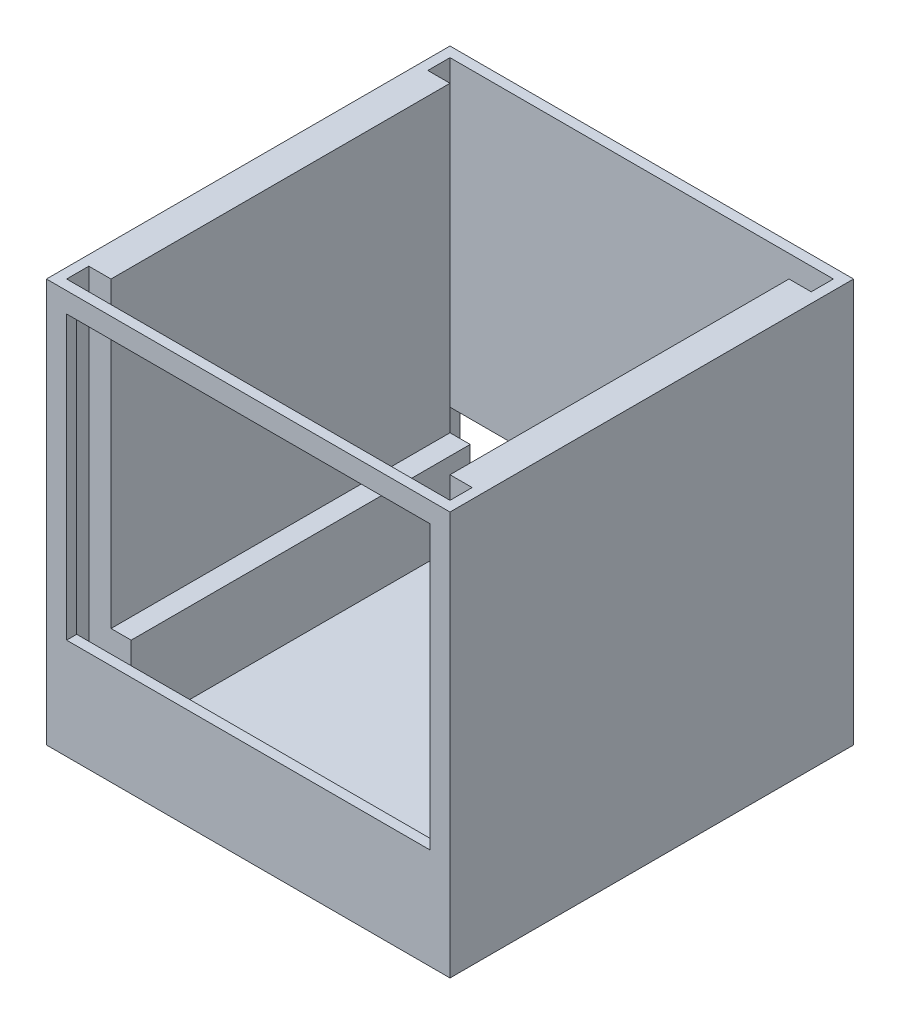
SolidWorks part; units mm, degrees
ref_plane "Front Plane" through (0, 0, 0) normal (0, 0, 1) x (1, 0, 0)
ref_plane "Top Plane" through (0, 0, 0) normal (0, 1, 0) x (1, 0, 0)
ref_plane "Right Plane" through (0, 0, 0) normal (1, 0, 0) x (0, 0, -1)
sketch "Sketch1" plane through (0, 0, 0) normal (0, 1, 0) x (1, 0, 0)
  line L0 (0, 127) -> (0, -127)
  line L1 (-127, -127) -> (127, -127)
  line L2 (-127, -127) -> (-127, 127)
  line L3 (-127, 127) -> (127, 127)
  line L4 (127, -127) -> (127, 127)
  line L5 (-127, -127) -> (127, 127) construction
  line L6 (-127, 127) -> (127, -127) construction
  line L7 (-120.65, -120.65) -> (120.65, -120.65)
  line L8 (-120.65, -120.65) -> (-120.65, 120.65)
  line L9 (-120.65, 120.65) -> (120.65, 120.65)
  line L10 (120.65, -120.65) -> (120.65, 120.65)
  line L11 (-120.65, -120.65) -> (120.65, 120.65) construction
  line L12 (-120.65, 120.65) -> (120.65, -120.65) construction
  line L13 (-120.65, 106.68) -> (-106.68, 106.68)
  line L14 (-120.65, 106.68) -> (-120.65, -106.68)
  line L15 (-120.65, -106.68) -> (-106.68, -106.68)
  line L16 (-106.68, 106.68) -> (-106.68, -106.68)
  line L17 (120.65, -106.68) -> (106.68, -106.68)
  line L18 (106.68, 106.68) -> (106.68, -106.68)
  line L19 (120.65, 106.68) -> (106.68, 106.68)
  line L20 (120.65, 106.68) -> (120.65, -106.68)
  point P0 (0, 0)
  point P6 (0, 0)
  point P21 (127, -127)
  dimension "D1" = 6.35
  dimension "D2" = 254
  dimension "D3" = 254
  dimension "D4" = 13.97
  dimension "D5" = 13.97
  dimension "D6" = 13.97
extrude "Boss-Extrude1" add sketch "Sketch1" along normal blind 190.5 contours L8 L9 L0 L3 L2 L1 L7 | L16 L13 L8 L15 | L10 L7 L0 L1 L4 L3 L9 | L10 L19 L18 L17 region at (63.5, 0, -124.1602) region at (-2.8398, 0, -123.825) region at (-113.665, 0, 0) region at (113.665, 0, 0)
sketch "Sketch4" plane through (0, 0, 0) normal (0, -1, 0) x (1, 0, 0)
  line L1 (-127, -127) -> (127, -127)
  line L2 (-127, -127) -> (-127, 127)
  line L3 (-127, 127) -> (127, 127)
  line L4 (127, -127) -> (127, 127)
  line L5 (120.65, 120.65) -> (-120.65, 120.65)
  line L6 (120.65, 120.65) -> (120.65, -120.65)
  line L7 (120.65, -120.65) -> (-120.65, -120.65)
  line L8 (-120.65, 120.65) -> (-120.65, -120.65)
  line L9 (-120.65, -120.65) -> (120.65, -120.65)
  line L10 (-120.65, -120.65) -> (-120.65, -127)
  line L11 (-120.65, -127) -> (120.65, -127)
  line L12 (120.65, -120.65) -> (120.65, -127)
  line M10 (-120.65, -120.65) -> (-120.65, -106.68)
  line M14 (-120.65, 106.68) -> (-120.65, 120.65)
  line M15 (-120.65, 120.65) -> (120.65, 120.65)
  line M16 (120.65, 120.65) -> (120.65, 106.68)
  line M20 (120.65, -106.68) -> (120.65, -120.65)
  line M21 (127, -127) -> (127, 127)
  line M22 (127, 127) -> (-127, 127)
  line M23 (-127, 127) -> (-127, -127)
  line M24 (-127, -127) -> (127, -127)
extrude "Boss-Extrude2" add sketch "Sketch4" along normal blind 50.8 contours L12 L10 L8 L6 M20 M24 M21 M22 M23 M10 M14 M15 M16 region at (-123.4079, 0, 0)
sketch "Sketch5" plane through (0, -50.8, 0) normal (0, -1, 0) x (1, 0, 0)
  line L1 (-127, 127) -> (127, 127)
  line L2 (-127, 127) -> (-127, -127)
  line L3 (-127, -127) -> (127, -127)
  line L4 (127, 127) -> (127, -127)
extrude "Boss-Extrude3" add sketch "Sketch5" along normal blind 12.7
sketch "Sketch6" plane through (0, 0, 127) normal (0, 0, 1) x (1, 0, 0)
  line L0 (-127, 0) -> (127, 0) construction
  line L1 (-114.3, 177.8) -> (114.3, 177.8)
  line L2 (-114.3, 177.8) -> (-114.3, 0)
  line L3 (-114.3, 0) -> (114.3, 0)
  line L4 (114.3, 177.8) -> (114.3, 0)
  line L5 (-127, 190.5) -> (127, 190.5) construction
  line L6 (-127, 190.5) -> (-127, -63.5) construction
  line L7 (127, 190.5) -> (127, -63.5) construction
  dimension "D1" = 12.7
  dimension "D2" = 12.7
  dimension "D3" = 12.7
extrude "Cut-Extrude1" cut sketch "Sketch6" against normal blind 12.7
extrude "Boss-Extrude5" add sketch "Sketch1<4>" against normal blind 50.8 contours L10 L19 L18 L17 | L16 L13 L8 L15 region at (-113.665, 0, 0) region at (113.665, 0, 0)
sketch "Sketch1<4>" plane through (0, 0, 0) normal (0, 1, 0) x (1, 0, 0) same geometry as "Sketch1"
sketch "Sketch8" plane through (0, -50.8, 0) normal (0, 1, 0) x (1, 0, 0)
  line L0 (-120.65, -106.68) -> (-106.68, -106.68) construction
  line L1 (-106.68, 106.68) -> (-93.98, 106.68)
  line L2 (-106.68, 106.68) -> (-106.68, -106.68)
  line L3 (-106.68, -106.68) -> (-93.98, -106.68)
  line L4 (-93.98, 106.68) -> (-93.98, -106.68)
  line L5 (0, 120.65) -> (0, -120.65)
  line L6 (-120.65, 120.65) -> (120.65, 120.65) construction
  line L7 (-120.65, -120.65) -> (120.65, -120.65) construction
  line L8 (106.68, -106.68) -> (93.98, -106.68)
  line L9 (93.98, 106.68) -> (93.98, -106.68)
  line L10 (106.68, 106.68) -> (93.98, 106.68)
  line L11 (106.68, 106.68) -> (106.68, -106.68)
  line M6 (-106.68, 106.68) -> (-106.68, -106.68)
  dimension "D1" = 0
  dimension "D2" = 12.7
extrude "Boss-Extrude6" add sketch "Sketch8" along normal blind 50.8 contours L4 L1 L3 M6 | L11 L8 L9 L10 region at (-100.33, -50.8, 0)
